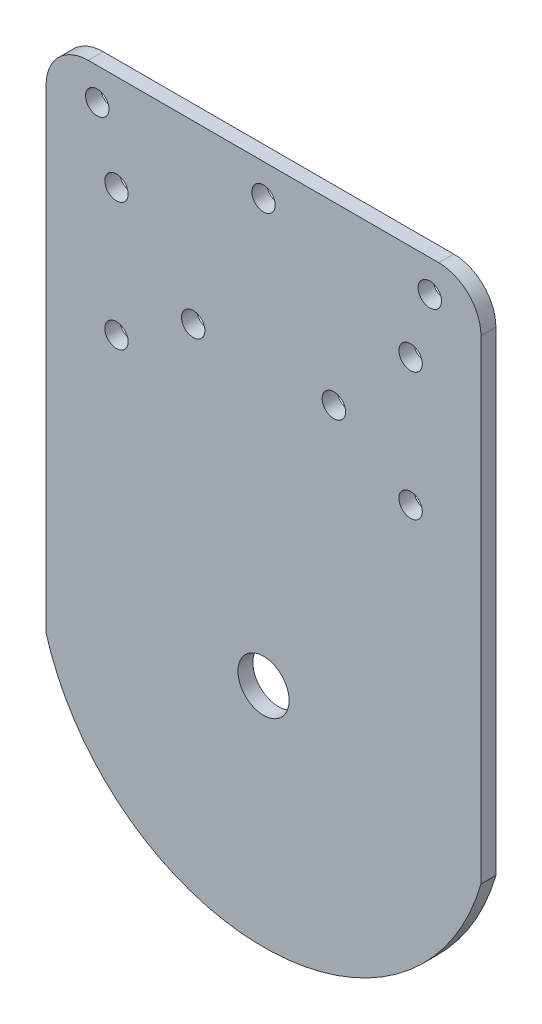
SolidWorks part; units mm, degrees
material "6061-T6 (SS)"
ref_plane "Front" through (0, 0, 0) normal (0, 0, 1) x (1, 0, 0)
ref_plane "Top" through (0, 0, 0) normal (0, 1, 0) x (1, 0, 0)
ref_plane "Right" through (0, 0, 0) normal (1, 0, 0) x (0, 0, -1)
ref_axis "side-side" through (80.9, 0, 0) along (-1, 0, 0)
ref_axis "up-down" through (0, 50, 0) along (0, -1, 0)
ref_axis "front-back" through (0, 0, -80.9) along (0, 0, 1)
sketch "Sketch2" plane through (0, 0, 0) normal (0, 0, 1) x (1, 0, 0)
  line L0 (23, 36) -> (23, 56) construction
  line L1 (23, 56) -> (26, 66) construction
  line L2 (26, 66) -> (0, 66) construction
  line L3 (34, 71) -> (-34, 71)
  line L4 (-34, 71) -> (-34, -9.857)
  line L5 (34, -9.857) -> (34, 71)
  line L6 (34, 71) -> (-34, 71)
  line L7 (-34, 71) -> (-34, -9.857)
  line L8 (34, -9.857) -> (34, 71)
  line L9 (0, 66) -> (11, 43.5) construction
  circle A1 centre (0, 0) radius 4
  circle A2 centre (0, 0) radius 4
  arc A3 (-34, -9.857) -> (34, -9.857) centre (0, 0) ccw
  arc A4 (-34, -9.857) -> (34, -9.857) centre (0, 0) ccw
  dimension "D1" = 0
  dimension "D2" = 0
sketch "Sketch1" plane through (0, 0, 0) normal (0, 0, 1) x (1, 0, 0)
  line L0 (-34, 71) -> (-34, -9.857) construction
  line L6 (34, -9.857) -> (34, 71) construction
  line L7 (34, 71) -> (-34, 71) construction
  line L8 (34, 71) -> (-34, 71)
  line L12 (-34, -9.857) -> (-34, 71)
  line L15 (34, -9.857) -> (34, 71)
  circle A1 centre (0, 0) radius 4
  circle A6 centre (0, 0) radius 8 construction
  arc A17 (-34, -9.857) -> (34, -9.857) centre (0, 0) ccw
  point P18 (34, 67.9347)
  point P21 (-34, -9.857)
  point P22 (34, 70.6713)
  point P23 (-46.3247, 71)
  point P29 (-34, 82.588)
  point P30 (34, -9.857)
  point P31 (0, 0)
  point P32 (34, 2.8691)
  point P34 (0, 0)
  dimension "D3" = 8
  dimension "D5" = 16
extrude "Boss-Extrude1" add sketch "Sketch1" along normal blind 2.3368
hole_wizard "#6 Clearance Hole1" positions "Sketch3" profile "Sketch4" hole size "#6" standard "ANSI Inch" end condition through all
sketch "Sketch3" plane through (0, 0, 2.3368) normal (0, 0, 1) x (1, 0, 0)
  line L0 (0, 0) -> (0, 82.7269) construction
  point P0 (0, 66)
  point P3 (11, 43.5)
  point P6 (23, 36)
  point P9 (23, 56)
  point P12 (26, 66)
  point P20 (-23, 36)
  point P22 (-11, 43.5)
  point P24 (-23, 56)
  point P26 (-26, 66)
  point P29 (0, 0)
  point P30 (0, 0)
  point P31 (0, 0)
  point P32 (0, 0)
sketch "Sketch4" plane through (0, 66, 2.3368) normal (1, 0, 0) x (0, -1, 0)
  line L0 (0, 0) -> (0, 2.3368)
  line L1 (0, 2.3368) -> (1.8288, 2.3368)
  line L2 (1.8288, 2.3368) -> (1.8288, 0)
  line L5 (1.8288, 0) -> (0, 0)
  line L11 (0, -6.35) -> (0, 107.95) construction
  dimension "Thru Hole Dia." = 3.6576
  dimension "Thru Hole Depth" = 2.3368
fillet "Fillet1" radius 6.6 2 edges at (34, 71, 1.1684) (-34, 71, 1.1684)
